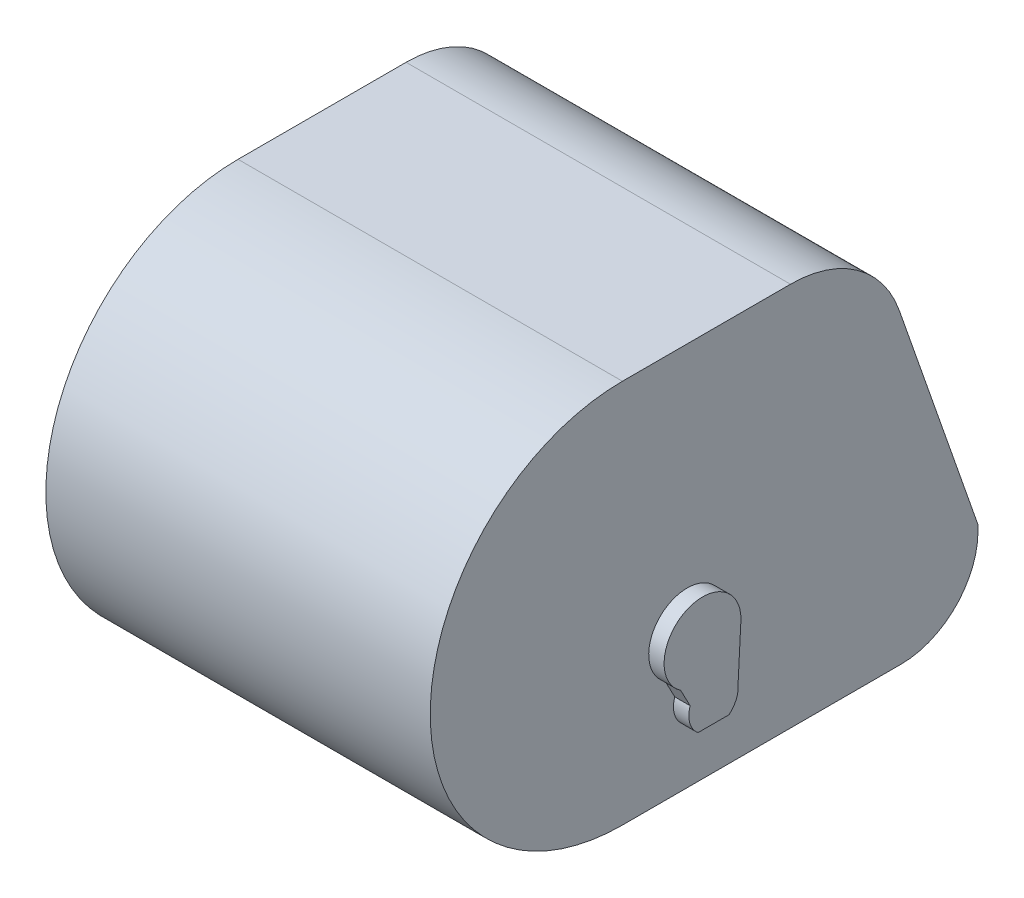
SolidWorks part; units mm, degrees
ref_plane "Front Plane" through (0, 0, 0) normal (0, 0, 1) x (1, 0, 0)
ref_plane "Top Plane" through (0, 0, 0) normal (0, 1, 0) x (1, 0, 0)
ref_plane "Right Plane" through (0, 0, 0) normal (1, 0, 0) x (0, 0, -1)
sketch "Sketch1" plane through (0, 0, 0) normal (1, 0, 0) x (0, 0, -1)
  line L0 (40, 50) -> (40, -50)
  line L1 (-75, -50) -> (75, -50)
  line L2 (-75, -50) -> (-75, 50)
  line L3 (-75, 50) -> (75, 50)
  line L4 (75, -50) -> (75, 50)
  line L5 (-75, -50) -> (75, 50) construction
  line L6 (-75, 50) -> (75, -50) construction
  line L7 (40, 50) -> (75, -50)
  line L8 (67.5, 50) -> (67.5, -50)
  circle A0 centre (-25, 0) radius 50
  point P0 (0, 0)
  dimension "D5" = 100
  dimension "D1" = 150
  dimension "D2" = 40
  dimension "D3" = 50
  dimension "D4" = 100
  dimension "D6" = 0
  dimension "D7" = 7.5
extrude "Boss-Extrude1" add sketch "Sketch1" along normal blind 50 and the other way blind 50 contours A0 | A0 L1 L0 L3 | L7 L0 L1 region at (0, -15.4062, -50.7843) region at (0, 0, -38.8073) region at (0, 0, 25)
fillet "Fillet1" radius 30 1 edges at (0, 50, -40)
sketch "Sketch5" plane through (50, 0, 0) normal (1, 0, 0) x (0, 0, -1)
  line L0 (47.0313, 29.9105) -> (15.0803, 1.384)
  line L1 (15.0803, 1.384) -> (59.8945, -6.8414)
  line L2 (47.0313, 29.9105) -> (67.5, -28.5714) construction
  line L3 (59.8945, -6.8414) -> (47.0313, 29.9105)
  dimension "D1" = 20
extrude "Cut-Extrude3" [suppressed] cut sketch "Sketch5" against normal blind 27
mirror "Mirror1" [suppressed] about plane through (0, 0, 0) normal (1, 0, 0)
sketch "Sketch6" plane through (50, 0, 0) normal (1, 0, 0) x (0, 0, -1)
  line L0 (-18.1629, -15) -> (-11.383, -27.9239)
  line L1 (-18.1629, -35) -> (1.8371, -35)
  line L2 (-18.1629, -35) -> (-18.1629, -5)
  line L3 (-18.1629, -5) -> (1.8371, -5)
  line L4 (1.8371, -35) -> (1.8371, -5)
  line L5 (-18.1629, -35) -> (1.8371, -5) construction
  line L6 (-18.1629, -5) -> (1.8371, -35) construction
  line L7 (1.8371, -15) -> (1.0758, -29.4031)
  line L8 (-25, -50) -> (67.5, -50) construction
  circle A0 centre (-8.1629, -15) radius 10
  circle A1 centre (-5.3123, -30) radius 6.4159
  point P0 (-8.1629, -20)
  dimension "D3" = 20
  dimension "D1" = 30
  dimension "D2" = 20
  dimension "D4" = 10
  dimension "D5" = 5
  dimension "D6" = 35
extrude "Boss-Extrude2" add sketch "Sketch6" along normal blind 4 contours L0 A0 | A1 A0 L7 L0 | A1 A0 L0 | L7 A1 A0 L0 | A1 L7 A0 | A0 A1 region at (50, -14.7585, 7.994) region at (50, -19.3276, 16.4123) region at (50, -25.4357, 11.5831) region at (50, -29.8507, 5.2703) region at (50, -24.2855, 6.3983) region at (50, -23.3086, -0.0625)
mirror "Mirror2" about plane through (0, 0, 0) normal (1, 0, 0) of "Boss-Extrude2"
sketch "Sketch7" plane through (50, 0, 0) normal (1, 0, 0) x (0, 0, -1)
  line L0 (50.1842, 20.9022) -> (51.7277, 16.4924)
  line L1 (47.0313, 29.9105) -> (67.5, -28.5714) construction
  line L2 (51.7277, 16.4924) -> (27.4141, 3.2585)
  line L3 (27.4141, 3.2585) -> (57.2657, 0.6695)
  line L4 (57.2657, 0.6695) -> (33.969, -2.2316)
  line L5 (35.3519, -4.401) -> (36.5796, -9.0228)
  line L6 (36.5796, -9.0228) -> (58.4476, -2.7076)
  line L7 (58.4476, -2.7076) -> (67.5, -28.5714)
  line L8 (50.1842, 20.9022) -> (58.4476, -2.7076)
  circle A0 centre (31.2494, -5.4907) radius 4.2448
  line M2 (67.5, -28.5714) -> (47.0313, 29.9105)
extrude "Cut-Extrude4" [suppressed] cut sketch "Sketch7" against normal blind 75 contours L2 L3 M2 | A0 L5 L6 L4 M2
fillet "Fillet4" radius 20 1 edges at (0, -50, -67.5)
sketch "Sketch8" plane through (0, -50, 0) normal (0, -1, 0) x (1, 0, 0)
  line L0 (-50, 75) -> (-50, 25) construction
  line L1 (0, -55) -> (0, 55) construction
  line L2 (-50, 55) -> (35.3328, 55)
  line L3 (-30, 75) -> (30, 75)
  line L5 (-50, 55) -> (50, 55)
  line L6 (-50, 55) -> (-50, 75)
  line L7 (-50, 75) -> (50, 75)
  line L8 (50, 55) -> (50, 75)
  arc A0 (-50, 55) -> (-30, 75) centre (-30, 55) cw
  arc A1 (50, 55) -> (30, 75) centre (30, 55) ccw
  dimension "D3" = 60
  dimension "D1" = 20
  dimension "D2" = 0
extrude "Cut-Extrude5" [suppressed] cut sketch "Sketch8" against normal blind 115 contours L6 A0 L7 | A1 L8 L7
sketch "Sketch9" plane through (0, 0, -67.5) normal (0, 0, -1) x (-1, 0, 0)
  line L0 (-11.3205, 29.9105) -> (-6.5587, 18.4632)
  line L1 (50, 29.9105) -> (-50, 29.9105) construction
  line L2 (-6.5587, 18.4632) -> (-6.5587, 9.9279)
  line L3 (-6.5587, 9.9279) -> (-50, 9.9279)
  line L4 (-50, 9.9279) -> (-50, 29.9105)
  line L5 (-50, 29.9105) -> (-11.3205, 29.9105)
extrude "Cut-Extrude6" [suppressed] cut sketch "Sketch9" against normal blind 28
mirror "Mirror3" [suppressed] about plane through (0, 0, 0) normal (1, 0, 0)
fillet "Fillet8" [suppressed] radius 2
